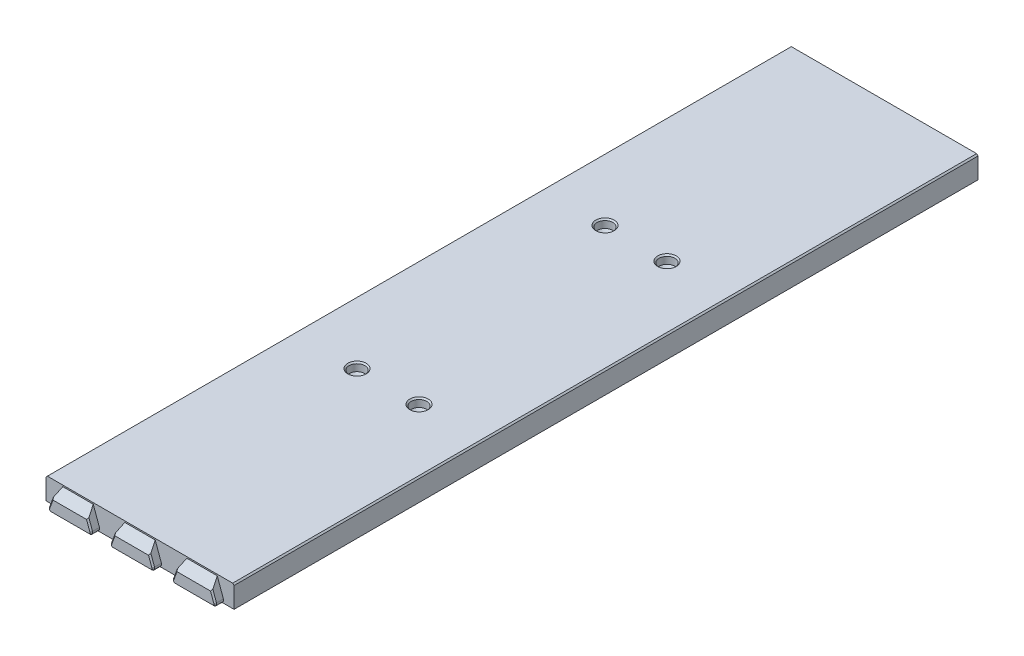
SolidWorks part; units mm, degrees
ref_plane "Front Plane" through (0, 0, 0) normal (0, 0, 1) x (1, 0, 0)
ref_plane "Top Plane" through (0, 0, 0) normal (0, 1, 0) x (1, 0, 0)
ref_plane "Right Plane" through (0, 0, 0) normal (1, 0, 0) x (0, 0, -1)
sketch "Sketch1" plane through (0, 0, 0) normal (0, 0, 1) x (1, 0, 0)
  line L0 (0, 0) -> (0, 8) construction
  line L1 (-34.125, 0) -> (0, 0) construction
  line L2 (-34.125, 0) -> (-34.125, 8)
  line L3 (-34.125, 8) -> (34.125, 8)
  line L5 (-34.125, 0) -> (-32.125, 0)
  line L6 (-32.125, 0) -> (-32.125, 6)
  line L7 (-32.125, 6) -> (32.125, 6)
  line L9 (32.125, 0) -> (32.125, 6)
  line L10 (34.125, 0) -> (32.125, 0)
  line L11 (34.125, 0) -> (34.125, 8)
  point P8 (0, 6)
  dimension "D2" = 6
  dimension "D1" = 34.125
  dimension "D3" = 2
  dimension "D4" = 2
extrude "Boss-Extrude1" add sketch "Sketch1" against normal blind 135
sketch "Sketch7" plane through (0, 0, 0) normal (0, 0, 1) x (1, 0, 0)
  line L2 (-32.125, 0) -> (32.125, 0)
  line L13 (-32.125, 0) -> (-32.125, 6)
  line L15 (-32.125, 6) -> (32.125, 6)
  line L16 (32.125, 0) -> (32.125, 6)
  line M3 (-32.125, 0) -> (-32.125, 6)
  line M4 (-32.125, 6) -> (32.125, 6)
  line M5 (32.125, 6) -> (32.125, 0)
extrude "Boss-Extrude7" add sketch "Sketch7" against normal blind 1 contours M4 M3 | M5 region at (0, 3, 0)
sketch "Sketch2" plane through (0, 0, 0) normal (0, 0, 1) x (1, 0, 0)
  line L14 (17.1618, 8) -> (14.25, 0)
  line L15 (34.125, 8) -> (-34.125, 8) construction
  line L16 (-34.125, 0) -> (34.125, 0) construction
  line L17 (14.25, 0) -> (30.75, 0)
  line L18 (17.1618, 8) -> (27.8382, 8)
  line L19 (-34.125, 0) -> (34.125, 0) construction
  line L21 (27.8382, 8) -> (30.75, 0)
  line L24 (11.25, 0) -> (11.25, 8) construction
  line L27 (-5.3382, 8) -> (-8.25, 0)
  line L28 (-5.3382, 8) -> (5.3382, 8)
  line L29 (-8.25, 0) -> (8.25, 0)
  line L30 (5.3382, 8) -> (8.25, 0)
  line L31 (-27.8382, 8) -> (-30.75, 0)
  line L32 (-27.8382, 8) -> (-17.1618, 8)
  line L33 (-30.75, 0) -> (-14.25, 0)
  line L34 (-17.1618, 8) -> (-14.25, 0)
  line L39 (17.1618, 8) -> (-5.3382, 8) construction
  line L40 (33.75, 8) -> (33.75, 0) construction
  line L41 (34.125, 0) -> (34.125, 8) construction
  line L42 (-33.75, 8) -> (-33.75, 0) construction
  line L43 (-34.125, 8) -> (-34.125, 0) construction
  point P22 (22.5, 8)
  point P23 (0, 8)
  dimension "D1" = 70
  dimension "D2" = 0.375
  dimension "D3" = 3
  dimension "D4" = 3
  dimension "D5" = 70
  dimension "D7" = 22.5
  dimension "D8" = 22.5
  dimension "D9" = 0.375
  dimension "D11" = 8
  dimension "D6" = 3
extrude "Boss-Extrude4" add sketch "Sketch2" along normal blind 3
sketch "Sketch8" plane through (0, 0, 0) normal (0, -1, 0) x (1, 0, 0)
  line L0 (-34.125, -22.5) -> (34.125, -22.5) construction
  line L1 (-32.6, -20.2583) -> (-28.9, -21.605)
  line L2 (34.125, -135) -> (34.125, 0) construction
  line L3 (-34.125, 0) -> (-30.75, 0) construction
  line L4 (-32.75, -24.9559) -> (-32.75, -20.0441) construction
  line L5 (-32.75, -20.0441) -> (-28.75, -21.5) construction
  line L6 (-28.75, -21.5) -> (-28.75, -23.5) construction
  line L7 (-32.75, -135) -> (-32.75, -132.5441) construction
  line L8 (-32.75, -132.5441) -> (-28.75, -134) construction
  line L9 (-28.75, -134) -> (-28.75, -135) construction
  line L10 (-32.125, -135) -> (32.125, -135) construction
  line L11 (-28.75, -135) -> (-32.75, -135) construction
  line L12 (-32.75, -24.9559) -> (-28.75, -23.5) construction
  line L13 (0, -135) -> (0, 0) construction
  line L22 (-28.9, -21.605) -> (-28.9, -23.395)
  line L23 (-34.125, -135) -> (-34.125, 0) construction
  line L28 (-34.125, -135) -> (-32.125, -135) construction
  line L33 (-32.6, -24.7417) -> (-28.9, -23.395)
  line L34 (-32.6, -24.7417) -> (-32.6, -20.2583)
  line L35 (-32.6, -132.7583) -> (-28.9, -134.105)
  line L36 (-28.9, -134.105) -> (-28.9, -134.85)
  line L37 (-28.9, -134.85) -> (-32.6, -134.85) construction
  line L38 (-32.6, -134.85) -> (-32.6, -132.7583)
  line L39 (-32.6, -134.85) -> (-32.6, -135)
  line L40 (-32.6, -135) -> (-28.9, -135)
  line L41 (-28.9, -135) -> (-28.9, -134.85)
  line L42 (32.6, -24.7417) -> (32.6, -20.2583)
  line L43 (32.6, -20.2583) -> (28.9, -21.605)
  line L44 (28.9, -21.605) -> (28.9, -23.395)
  line L45 (32.6, -24.7417) -> (28.9, -23.395)
  line L46 (32.6, -134.85) -> (32.6, -135)
  line L47 (28.9, -135) -> (28.9, -134.85)
  line L48 (32.6, -135) -> (28.9, -135)
  line L49 (28.9, -134.105) -> (28.9, -134.85)
  line L50 (32.6, -132.7583) -> (28.9, -134.105)
  line L51 (32.6, -134.85) -> (32.6, -132.7583)
  point P19 (-28.75, -22.5)
  dimension "D1" = 22.5
  dimension "D2" = 1.375
  dimension "D3" = 70
  dimension "D4" = 4
  dimension "D5" = 0.15
  dimension "D6" = 4
  dimension "D7" = 70
  dimension "D8" = 1
  dimension "D9" = 1
  dimension "D10" = 0.15
extrude "Boss-Extrude8" add sketch "Sketch8" against normal up to next and the other way blind 2
chamfer "Chamfer4" distance 0.5 angle 45 14 edges at (30.75, -2, -20.9317) (32.6, -2, -22.5) (30.75, -2, -24.0683) (28.9, -2, -22.5) (-30.75, -2, -20.9317) (-28.9, -2, -22.5) (-30.75, -2, -24.0683) (-32.6, -2, -22.5) (-28.9, -2, -134.5525) (-32.6, -2, -133.8792) (-30.75, -2, -133.4317) (28.9, -2, -134.5525) (30.75, -2, -133.4317) (32.6, -2, -133.8792)
fillet "Fillet4" radius 1 6 edges at (30.75, 0, 1.5) (14.25, 0, 1.5) (8.25, 0, 1.5) (-8.25, 0, 1.5) (-14.25, 0, 1.5) (-30.75, 0, 1.5)
chamfer "Chamfer6" distance 0.5 angle 45 15 edges at (15.9501, 4.671, 3) (29.0499, 4.671, 3) (22.5, 0, 3) (-29.0499, 4.671, 3) (-22.5, 0, 3) (-15.9501, 4.671, 3) (-6.5499, 4.671, 3) (6.5499, 4.671, 3) (0, 0, 3) (-30.141, 0.4264, 3) (-14.859, 0.4264, 3) (-7.641, 0.4264, 3) (7.641, 0.4264, 3) (14.859, 0.4264, 3) (30.141, 0.4264, 3)
fillet "Fillet2" radius 2 22 edges at (0, 6, -1) (-32.125, 3, -1) (32.125, 6, -10.7156) (32.125, 3, -1) (-32.125, 6, -10.7156) (32.125, 3, -132.9312) (28.9, 6, -134.5525) (30.5125, 6, -133.5181) (-28.9, 6, -134.5525) (-32.125, 3, -132.9312) (-30.5125, 6, -133.5181) (-30.5125, 6, -21.0181) (28.9, 6, -22.5) (30.5125, 6, -21.0181) (32.125, 3, -20.4312) (32.125, 3, -24.5688) (30.5125, 6, -23.9819) (32.125, 6, -78.75) (-28.9, 6, -22.5) (-30.5125, 6, -23.9819) (-32.125, 3, -24.5688) (-32.125, 6, -78.75)
mirror "Mirror2" about plane through (0, 0, -135) normal (0, 0, 1) of "Fillet4", "Boss-Extrude1", "Boss-Extrude7", "Boss-Extrude4", "Boss-Extrude8", "Chamfer4", "Fillet2", "Chamfer6"
sketch "Sketch9" plane through (0, 0, 0) normal (0, 1, 0) x (1, 0, 0)
  line L16 (0, 135) -> (0, 0) construction
  line L17 (-34.125, 135) -> (34.125, 135) construction
  line L20 (34.125, 270) -> (34.125, 0) construction
  line L21 (-34.125, 270) -> (-34.125, 0) construction
  circle A0 centre (-11.25, 90) radius 5
  circle A4 centre (11.25, 90) radius 5
  circle A5 centre (11.25, 180) radius 5
  circle A6 centre (-11.25, 180) radius 5
  point P23 (0, 135)
  point P24 (0, 135)
  dimension "D3" = 10
  dimension "D1" = 11.25
  dimension "D2" = 45
extrude "Boss-Extrude9" add sketch "Sketch9" along normal up to next
fillet "Fillet3" radius 3 4 edges at (-11.25, 6, -95) (11.25, 6, -185) (-11.25, 6, -185) (11.25, 6, -95)
sketch "Sketch10" plane through (0, 0, 0) normal (0, 1, 0) x (1, 0, 0)
  circle A0 centre (-11.25, 180) radius 1.85
  circle A1 centre (-11.25, 90) radius 1.85
  circle A2 centre (11.25, 90) radius 1.85
  circle A3 centre (11.25, 180) radius 1.85
  dimension "D1" = 3.7
extrude "Cut-Extrude2" cut sketch "Sketch10" along normal through all
sketch "Sketch11" plane through (0, 8, 0) normal (0, 1, 0) x (1, 0, 0)
  circle A0 centre (-11.25, 180) radius 2.85
  circle A1 centre (11.25, 180) radius 2.85
  circle A2 centre (11.25, 90) radius 2.85
  circle A3 centre (-11.25, 90) radius 2.85
  dimension "D1" = 5.7
extrude "Cut-Extrude3" cut sketch "Sketch11" against normal blind 3
chamfer "Chamfer7" distance 1 angle 45 4 edges at (11.25, 5, -178.15) (-11.25, 5, -178.15) (11.25, 5, -88.15) (-11.25, 5, -88.15)
sketch "Sketch12" plane through (0, 0, 0) normal (1, 0, 0) x (0, 0, -1)
  line L0 (0, 7.5) -> (-3, 4.5)
  line L1 (-3, 1.171) -> (-3, 8) construction
  line L2 (-3, 4.5) -> (-3, 7.5)
  line L3 (-3, 7.5) -> (0, 7.5) construction
  line L4 (135, 8) -> (135, 0) construction
  line L5 (270, 8) -> (0, 8) construction
  line L6 (270, 0) -> (0, 0) construction
  line L10 (0, 1.342) -> (0, 8) construction
  line L11 (-3, 7.5) -> (-3, 8)
  line L12 (-3, 8) -> (0, 8)
  line L13 (0, 8) -> (0, 7.5)
  line L14 (273, 7.5) -> (270, 7.5) construction
  line L15 (270, 8) -> (270, 7.5)
  line L16 (273, 8) -> (270, 8)
  line L17 (273, 7.5) -> (273, 8)
  line L18 (273, 4.5) -> (273, 7.5)
  line L19 (270, 7.5) -> (273, 4.5)
  dimension "D1" = 45
  dimension "D2" = 3
  dimension "D3" = 0.5
extrude "Cut-Extrude4" cut sketch "Sketch12" against normal through all both and the other way through all
chamfer "Chamfer8" distance 0.5 angle 45 6 edges at (34.125, 8, -135) (-34.125, 8, -135) (-11.25, 8, -177.15) (11.25, 8, -177.15) (11.25, 8, -87.15) (-11.25, 8, -87.15)
